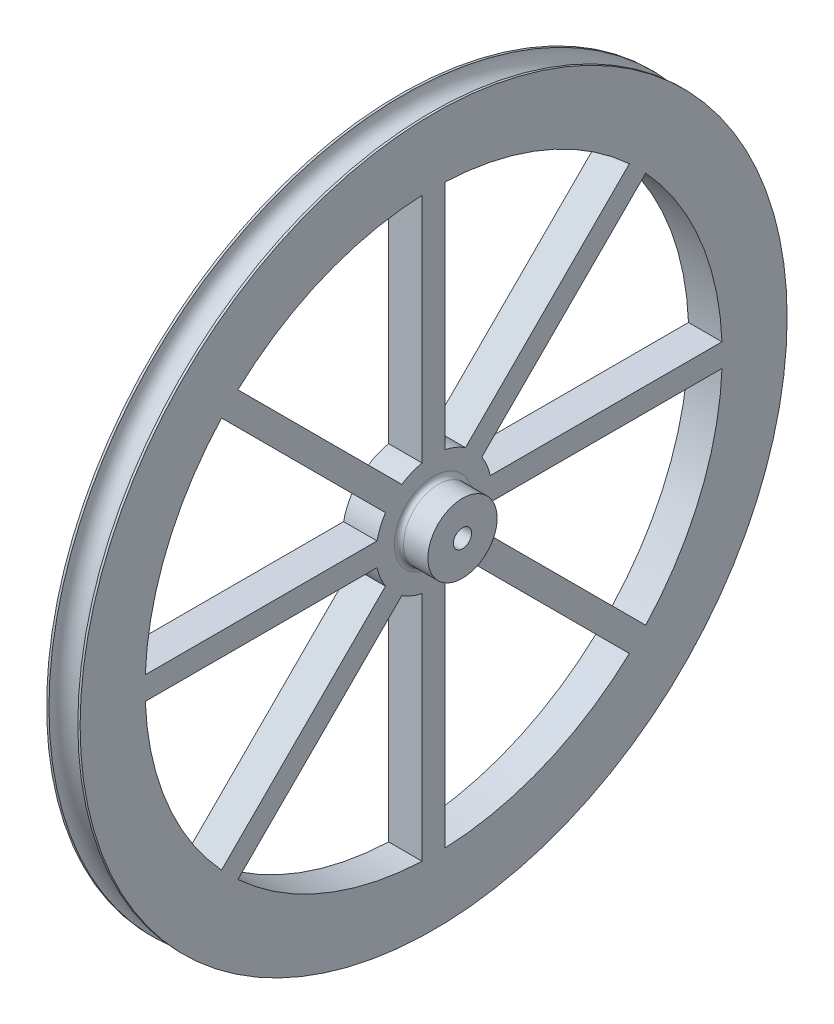
SolidWorks part; units mm, degrees
ref_plane "Front Plane" through (0, 0, 0) normal (0, 0, 1) x (1, 0, 0)
ref_plane "Top Plane" through (0, 0, 0) normal (0, 1, 0) x (1, 0, 0)
ref_plane "Right Plane" through (0, 0, 0) normal (1, 0, 0) x (0, 0, -1)
sketch "Sketch1" plane through (0, 0, 0) normal (1, 0, 0) x (0, 0, -1)
  circle A0 centre (0, 0) radius 38.8938
  dimension "D1" = 77.7875
extrude "Boss-Extrude1" add sketch "Sketch1" along normal blind 3.683
sketch "Sketch10" plane through (0, 0, 0) normal (0, 0, 1) x (1, 0, 0)
  line L0 (3.683, 38.8938) -> (0, 38.8938) construction
  line L1 (-1.0162, 0) -> (5.466, 0) construction
  line L2 (55, 0) -> (-55, 0) construction
  circle A0 centre (1.8415, 38.8938) radius 1.5875
  dimension "D1" = 3.175
revolve "Cut-Revolve1" cut sketch "Sketch10" angle 360 about L1
sketch "Sketch11" plane through (3.683, 0, 0) normal (1, 0, 0) x (0, 0, -1)
  line L2 (0, -50.6508) -> (0, 43.6326) construction
  line L3 (-53.144, 0) -> (6.35, 0) construction
  line L4 (-1.27, 31.7246) -> (-1.27, 6.2217)
  line L5 (1.27, 31.7246) -> (1.27, 6.2217)
  line L6 (21.5346, 23.3307) -> (3.5014, 5.2974)
  line L7 (23.3307, 21.5346) -> (5.2974, 3.5014)
  line L8 (31.7246, 1.27) -> (6.2217, 1.27)
  line L9 (31.7246, -1.27) -> (6.2217, -1.27)
  line L10 (23.3307, -21.5346) -> (5.2974, -3.5014)
  line L11 (21.5346, -23.3307) -> (3.5014, -5.2974)
  line L12 (1.27, -31.7246) -> (1.27, -6.2217)
  line L13 (-1.27, -31.7246) -> (-1.27, -6.2217)
  line L14 (-21.5346, -23.3307) -> (-3.5014, -5.2974)
  line L15 (-23.3307, -21.5346) -> (-5.2974, -3.5014)
  line L16 (-31.7246, -1.27) -> (-6.2217, -1.27)
  line L17 (-31.7246, 1.27) -> (-6.2217, 1.27)
  line L18 (-23.3307, 21.5346) -> (-5.2974, 3.5014)
  line L19 (-21.5346, 23.3307) -> (-3.5014, 5.2974)
  arc A2 (5.2974, -3.5014) -> (6.2217, -1.27) centre (0, 0) ccw
  arc A3 (-23.3307, 21.5346) -> (-31.7246, 1.27) centre (0, 0) ccw
  arc A4 (21.5346, 23.3307) -> (1.27, 31.7246) centre (0, 0) ccw
  arc A5 (-1.27, 31.7246) -> (-21.5346, 23.3307) centre (0, 0) ccw
  arc A6 (31.7246, 1.27) -> (23.3307, 21.5346) centre (0, 0) ccw
  arc A7 (23.3307, -21.5346) -> (31.7246, -1.27) centre (0, 0) ccw
  arc A8 (1.27, -31.7246) -> (21.5346, -23.3307) centre (0, 0) ccw
  arc A9 (-21.5346, -23.3307) -> (-1.27, -31.7246) centre (0, 0) ccw
  arc A10 (-31.7246, -1.27) -> (-23.3307, -21.5346) centre (0, 0) ccw
  arc A11 (1.27, -6.2217) -> (3.5014, -5.2974) centre (0, 0) ccw
  arc A12 (-3.5014, -5.2974) -> (-1.27, -6.2217) centre (0, 0) ccw
  arc A13 (-6.2217, -1.27) -> (-5.2974, -3.5014) centre (0, 0) ccw
  arc A14 (-5.2974, 3.5014) -> (-6.2217, 1.27) centre (0, 0) ccw
  arc A15 (-1.27, 6.2217) -> (-3.5014, 5.2974) centre (0, 0) ccw
  arc A16 (3.5014, 5.2974) -> (1.27, 6.2217) centre (0, 0) ccw
  arc A17 (6.2217, 1.27) -> (5.2974, 3.5014) centre (0, 0) ccw
  point P43 (0, 0)
  dimension "D1" = 12.7
  dimension "D2" = 63.5
  dimension "D3" = 2.54
  dimension "D4" = 1.27
  dimension "D5" = 8
extrude "Cut-Extrude3" cut sketch "Sketch11" against normal through all
sketch "Sketch12" plane through (3.683, 0, 0) normal (1, 0, 0) x (0, 0, -1)
  circle A0 centre (0, 0) radius 1
  dimension "D1" = 2
extrude "Cut-Extrude4" cut sketch "Sketch12" against normal through all
sketch "Sketch13" plane through (3.683, 0, 0) normal (1, 0, 0) x (0, 0, -1)
  circle A0 centre (0, 0) radius 3.81
  circle A1 centre (0, 0) radius 1
  dimension "D1" = 7.62
  dimension "D2" = 2
extrude "Boss-Extrude2" add sketch "Sketch13" along normal blind 3.175
fillet "Fillet1" radius 0.508 1 edges at (3.683, 0, -3.81)
